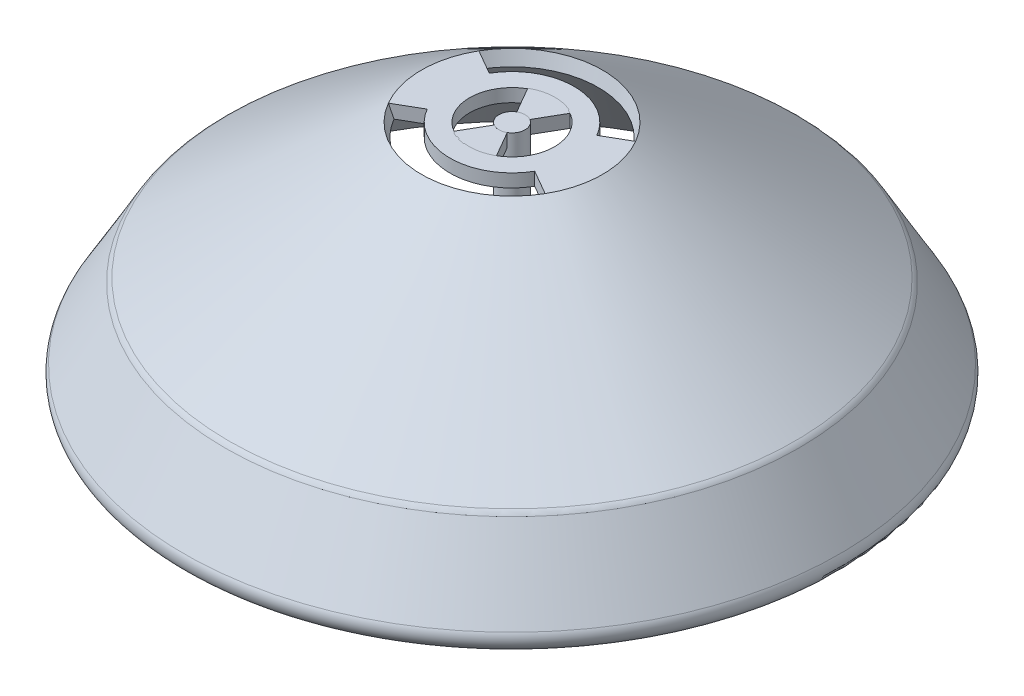
SolidWorks part; units mm, degrees
ref_plane "Front Plane" through (0, 0, 0) normal (0, 0, 1) x (1, 0, 0)
ref_plane "Top Plane" through (0, 0, 0) normal (0, 1, 0) x (1, 0, 0)
ref_plane "Right Plane" through (0, 0, 0) normal (1, 0, 0) x (0, 0, -1)
sketch "Sketch1" plane through (0, 0, 0) normal (0, 0, 1) x (1, 0, 0)
  line L1 (9.525, 104.902) -> (9.525, 95.25)
  line L2 (3.683, 97.79) -> (3.683, 95.25)
  line L4 (3.683, 95.25) -> (9.525, 95.25)
  line L5 (3.683, 97.79) -> (6.35, 97.79)
  line L6 (-9.525, 104.902) -> (-9.525, 95.25)
  line L9 (-3.683, 95.25) -> (-9.525, 95.25)
  line L13 (-3.683, 97.79) -> (-3.683, 95.25)
  line L16 (-3.683, 97.79) -> (-6.35, 97.79)
  line L17 (-9.525, 104.902) -> (9.525, 104.902)
  line L18 (-6.35, 97.79) -> (-6.35, 101.6)
  line L19 (0, 133.35) -> (0, 94.2799)
  line L20 (6.35, 101.6) -> (9.525, 101.6)
  line L21 (-6.35, 101.6) -> (6.35, 101.6)
  line L22 (6.35, 101.6) -> (6.35, 97.79)
  line L24 (8.255, 133.35) -> (8.255, 130.81)
  line L25 (12.065, 133.35) -> (12.065, 130.81)
  line L28 (9.525, 101.6) -> (-6.35, 101.6)
  line L31 (-6.35, 101.6) -> (-9.525, 101.6)
  line L32 (0, 130.81) -> (16.7852, 130.81)
  line L33 (16.7852, 130.81) -> (53.5102, 105.0949)
  line L34 (53.5102, 105.0949) -> (62.7536, 89.0848)
  line L35 (-2.54, 133.35) -> (-2.54, 104.902)
  line L36 (62.2037, 88.7673) -> (64.9533, 90.3548) construction
  line L37 (2.54, 133.35) -> (2.54, 104.902)
  line L38 (-62.7536, 89.0848) -> (-64.9533, 90.3548)
  line L39 (-55.4283, 106.8526) -> (-64.9533, 90.3548)
  line L40 (-53.5102, 105.0949) -> (-62.7536, 89.0848)
  line L41 (-8.255, 133.35) -> (-8.255, 130.81)
  line L42 (-12.065, 133.35) -> (-12.065, 130.81)
  line L43 (-16.7852, 130.81) -> (-53.5102, 105.0949)
  line L44 (-17.5861, 133.35) -> (-55.4283, 106.8526)
  line L45 (0, 133.35) -> (-17.5861, 133.35)
  line L46 (0, 130.81) -> (-16.7852, 130.81)
  line L47 (-17.5861, 133.35) -> (-16.7852, 130.81)
  line L48 (2.54, 133.35) -> (2.54, 94.2799) construction
  line L49 (-2.54, 133.35) -> (-2.54, 94.2799) construction
  line L50 (17.5861, 133.35) -> (16.7852, 130.81)
  line L73 (0, 133.35) -> (17.5861, 133.35)
  line L74 (17.5861, 133.35) -> (55.4283, 106.8526)
  line L78 (55.4283, 106.8526) -> (64.9533, 90.3548)
  line L82 (62.7536, 89.0848) -> (64.9533, 90.3548)
  line L86 (10.16, 133.35) -> (10.16, 130.81) construction
  line L90 (-55.4283, 106.8526) -> (-64.9533, 90.3548)
  line L92 (-17.5861, 133.35) -> (-55.4283, 106.8526)
  line L104 (0, 133.35) -> (-17.5861, 133.35)
  line L105 (60.9337, 90.967) -> (61.4836, 91.2845) construction
  line L106 (53.5102, 105.0949) -> (61.4836, 91.2845) construction
  point P11 (3.81, 25.4)
  point P14 (10.7436, 6.35)
  point P18 (-0.6484, 19.0832)
  point P19 (6.2973, 0)
  point P24 (12.7, 0)
  point P26 (12.7, 25.4)
  point P28 (0, 38.1)
  point P31 (12.1451, 41.8131)
  point P32 (0, 38.1)
  point P33 (19.05, 38.1)
  point P57 (0, 101.6)
  point P72 (-1.27, 101.6)
  point P73 (-1.27, -11.7576)
  point P74 (1.27, 101.6)
  point P75 (1.27, -11.7576)
  point P84 (0, 104.902)
  point P94 (-3.81, 104.902)
  dimension "D1" = 2.54
  dimension "D2" = 2.54
  dimension "D3" = 2.54
  dimension "D4" = 1.905
  dimension "D5" = 1.905
  dimension "D6" = 7.366
  dimension "D7" = 12.7
  dimension "D8" = 19.05
  dimension "D9" = 38.1
  dimension "D10" = 44.2652
revolve "Revolve4" add sketch "Sketch1" angle 360 about L19 region at (4.7625, 103.251, 0)
revolve "Revolve5" add sketch "Sketch1<21>" angle 90 mid plane about L19 region at (7.2029, 97.9459, 0) region at (-7.2029, 97.9459, 0)
sketch "Sketch1<21>" plane through (0, 0, 0) normal (0, 0, 1) x (1, 0, 0) same geometry as "Sketch1"
revolve "Revolve7" add sketch "Sketch1<24>" angle 360 about L19 region at (1.27, 117.856, 0) region at (1.27, 132.08, 0) region at (10.16, 132.08, 0) region at (42.6441, 112.8479, 0)
sketch "Sketch1<24>" plane through (0, 0, 0) normal (0, 0, 1) x (1, 0, 0) same geometry as "Sketch1"
revolve "Revolve9" add sketch "Sketch1<29>" angle 60 mid plane about L19 region at (14.6306, 132.1131, 0) region at (-14.6306, 132.1131, 0)
sketch "Sketch1<29>" plane through (0, 0, 0) normal (0, 0, 1) x (1, 0, 0) same geometry as "Sketch1"
sketch "Sketch2" plane through (0, 0, 0) normal (1, 0, 0) x (0, 0, -1)
  line L0 (0, 133.35) -> (0, 130.81)
  line L1 (8.7931, 133.35) -> (-8.7931, 133.35) construction
  line L2 (-23.1679, 130.81) -> (23.1679, 130.81)
  line L3 (0, 133.35) -> (0, 130.8026)
  line L5 (-2.54, 133.35) -> (2.54, 133.35)
  line L6 (2.54, 133.35) -> (10.922, 133.35) construction
  line L7 (-8.382, 133.35) -> (8.382, 133.35)
  line L8 (8.382, 133.35) -> (8.382, 130.81)
  line L10 (2.54, 130.81) -> (2.54, 133.35)
  line L11 (-8.382, 133.35) -> (-8.382, 130.81)
  line L12 (-2.54, 130.81) -> (-2.54, 133.35)
revolve "Revolve10" add sketch "Sketch2" angle 60 mid plane about L0 region at (0, 132.08, 5.461) region at (0, 132.08, -5.461)
fillet "Fillet1" radius 2.54 1 edges at (0, 90.3548, 64.9533)
fillet "Fillet2" radius 2.54 1 edges at (0, 106.8526, 55.4283)
